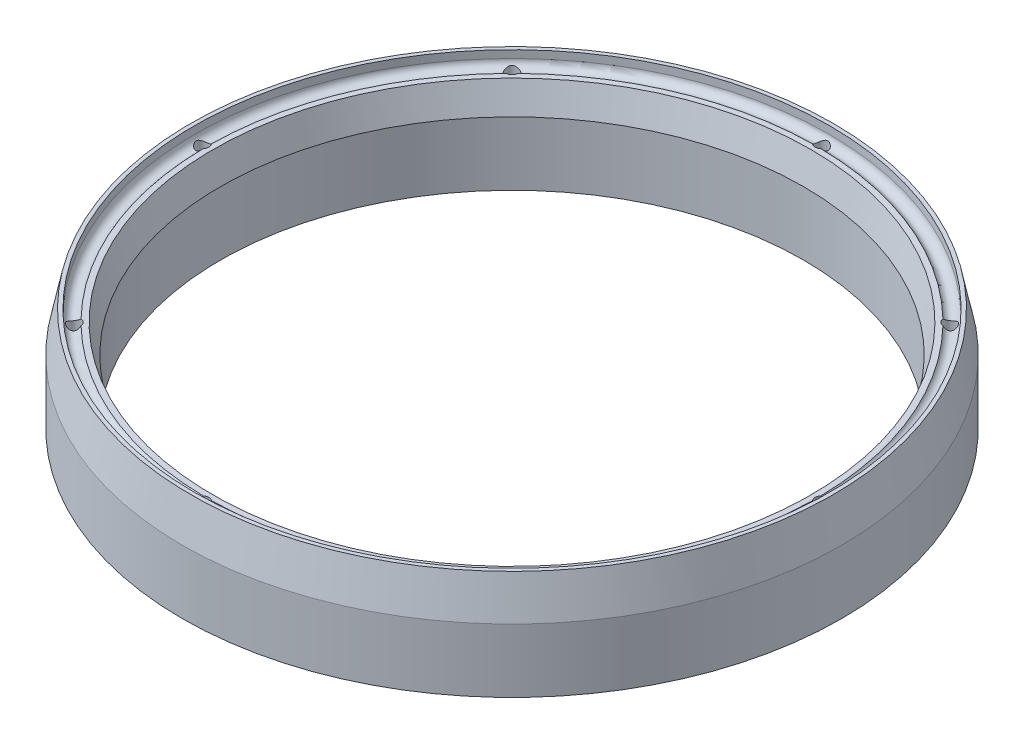
SolidWorks part; units mm, degrees
ref_plane "Front" through (0, 0, 0) normal (0, 0, 1) x (1, 0, 0)
ref_plane "Top" through (0, 0, 0) normal (0, 1, 0) x (1, 0, 0)
ref_plane "Right" through (0, 0, 0) normal (1, 0, 0) x (0, 0, -1)
sketch "Sketch3" plane through (0, 0, 0) normal (0, 0, 1) x (1, 0, 0)
  line L0 (86.2847, 16.6445) -> (86.2847, 0)
  line L1 (76.2847, 0) -> (0, 0) construction
  line L3 (76.2847, 0) -> (76.2847, 16.6445)
  line L4 (0, 0) -> (0, 10) construction
  line L5 (81.2847, 25.0416) -> (81.2847, 0) construction
  line L6 (76.2847, 16.6445) -> (78.5347, 25.0416)
  line L7 (78.5347, 25.0416) -> (84.0347, 25.0416)
  line L8 (76.2847, 0) -> (86.2847, 0)
  line L9 (84.0347, 25.0416) -> (86.2847, 16.6445)
  circle A0 centre (81.2847, 25.0416) radius 1.7653 construction
  circle A1 centre (0, 213.2) radius 203.2 construction
  dimension "D4" = 406.4
  dimension "D6" = 10
  dimension "D2" = 3.5306
  dimension "D3" = 166.1
  dimension "D5" = 5.5
  dimension "D7" = 30
  dimension "D8" = 0
  dimension "D10" = 10
revolve "Revolve1" add sketch "Sketch3" angle 360 about L4
sketch "Sketch8" plane through (0, 0, 0) normal (0, 0, 1) x (1, 0, 0)
  line L0 (0, 0) -> (0, 25.0416) construction
  line L2 (84.0347, 25.0416) -> (78.5347, 25.0416)
  line L3 (-78.6871, 24.8918) -> (-83.1871, 24.8918)
  line L4 (78.5347, 25.0416) -> (-78.5347, 25.0416) construction
  line L5 (84.0347, 25.0416) -> (78.5347, 25.0416) construction
  circle A0 centre (81.2847, 25.0416) radius 1.825
  dimension "D1" = 3.65
revolve "Cut-Revolve1" cut sketch "Sketch8" angle 360 about L0
sketch "Sketch15" plane through (0, 0, 0) normal (0, 0, 1) x (1, 0, 0)
  line L0 (81.2847, 25.0416) -> (78.5347, 25.0416)
  line L1 (78.5347, 25.0416) -> (84.0347, 25.0416) construction
  line L2 (78.5347, 25.0416) -> (78.2668, 24.0416)
  line L3 (76.2847, 16.6445) -> (78.5347, 25.0416) construction
  line L4 (78.2668, 24.0416) -> (81.2847, 24.0416)
  line L5 (81.2847, 25.0416) -> (81.2847, 0) construction
  line L6 (81.2847, 24.0416) -> (81.2847, 25.0416)
  line L7 (0, 0) -> (0, 25.0416) construction
  line L8 (78.5347, 25.0416) -> (-78.5347, 25.0416) construction
  dimension "D1" = 1
revolve "Cut-Revolve3" cut sketch "Sketch15" angle 360 about L7
sketch "Sketch17" plane through (0, 0, 0) normal (0, 0, 1) x (1, 0, 0)
  line L1 (84.1097, 27.0416) -> (83.1097, 27.0416)
  line L2 (83.1097, 27.0416) -> (83.1097, 25.0416)
  line L3 (78.5347, 25.0416) -> (84.0347, 25.0416) construction
  line L4 (83.1097, 25.0416) -> (84.0347, 25.0416)
  line L5 (86.2847, 16.6445) -> (84.1097, 27.0416)
  line L6 (84.0347, 25.0416) -> (86.2847, 16.6445)
  line L7 (0, 0) -> (0, 25.0416) construction
  circle A0 centre (81.2847, 25.0416) radius 1.825 construction
  dimension "D1" = 1
  dimension "D2" = 2
revolve "Revolve3" add sketch "Sketch17" angle 360 about L7
fillet "Fillet1" [suppressed] radius 1
hole_wizard "M4x0.7 Tapped Hole1" positions "Sketch9" profile "Sketch10" tap size "M4x0.7" standard "ANSI Metric" end condition through all
sketch "Sketch9" plane through (0, 0, 0) normal (0, -1, 0) x (-1, 0, 0)
  line L0 (-81, 0) -> (0, 0) construction
  circle A0 centre (0, 0) radius 81
  point P0 (0, -81)
  dimension "D1" = 162
cosmetic thread "Hole Thread1" [suppressed] parameters "D2"=4
sketch "Sketch10" plane through (0, 0, 81) normal (1, 0, 0) x (0, 0, -1)
  line L0 (0, 0) -> (0, 27.0416)
  line L1 (0, 27.0416) -> (1.65, 27.0416)
  line L2 (1.65, 27.0416) -> (1.65, 0)
  line L5 (1.65, 0) -> (0, 0)
  line L11 (0, -6.35) -> (0, 107.95) construction
  dimension "Thru Tap Drill Dia." = 3.3
  dimension "Thru Tap Drill Depth" = 27.0416
pattern_circular "CirPattern1" count 8 over 360 about axis through (0, 0, 0) along (0, -1, 0) of "M4x0.7 Tapped Hole1"
sketch "Sketch11" plane through (0, 0, 0) normal (0, 0, 1) x (1, 0, 0)
  line L0 (76.2847, 0) -> (71.2847, -60)
  line L1 (71.2847, -60) -> (91.2847, -60)
  line L2 (91.2847, -60) -> (86.2847, 0)
  line L3 (81.2847, 0) -> (81.2847, -60) construction
  line L4 (0, 0) -> (0, 10) construction
  line L5 (76.2847, 0) -> (86.2847, 0)
  dimension "D1" = 60
  dimension "D2" = 20
revolve "Revolve2" [suppressed] add sketch "Sketch11" angle 360 about L4
fillet "Fillet14" [suppressed] type full round
sketch "Sketch12" [suppressed] plane through (0, 0, 0) normal (0, 0, 1) x (1, 0, 0)
  line L0 (0, 0) -> (0, -60) construction
  line L2 (-17.5, 0) -> (17.5, 0)
  line L3 (86.7347, 0) -> (-86.7347, 0) construction
  line L4 (76.7347, 0) -> (0, 0) construction
  line L5 (17.5, 0) -> (28.0796, -60)
  line L6 (28.0796, -60) -> (-28.0796, -60)
  line L7 (-28.0796, -60) -> (-17.5, 0)
  dimension "D1" = 35
  dimension "D2" = 80
  dimension "D3" = 60
extrude "Cut-Extrude1" [suppressed] cut sketch "Sketch12" along normal through all
pattern_circular "CirPattern2" [suppressed] count 6 over 360 of bodies 118
fillet "Fillet2" [suppressed] type full round
fillet "Fillet5" [suppressed] type full round
fillet "Fillet6" [suppressed] type full round
fillet "Fillet7" [suppressed] type full round
fillet "Fillet8" [suppressed] type full round
fillet "Fillet9" [suppressed] type full round
fillet "Fillet3" [suppressed] radius 16
fillet "Fillet11" [suppressed] type full round
fillet "Fillet12" [suppressed] type full round
fillet "Fillet15" [suppressed] type full round
fillet "Fillet16" [suppressed] type full round
fillet "Fillet17" [suppressed] type full round
fillet "Fillet18" [suppressed] type full round
fillet "Fillet19" [suppressed] radius 10
sketch "Sketch13" [suppressed] plane through (0, 0, 0) normal (0, 0, 1) x (1, 0, 0)
  line L0 (79.4835, 25.2429) -> (-79.4835, 25.2429) construction
  line L1 (-86.7347, 25.3867) -> (86.7347, 25.3867)
  line L2 (-86.7347, 25.3867) -> (-86.7347, 17.9226)
  line L3 (-86.7347, 17.9226) -> (86.7347, 17.9226)
  line L4 (86.7347, 25.3867) -> (86.7347, 17.9226)
  line L5 (0, 17.9226) -> (0, 25.3867) construction
  line L6 (-86.7347, 21.6546) -> (86.7347, 21.6546) construction
  point P396 (0, 21.6546)
extrude "Cut-Extrude2" [suppressed] cut sketch "Sketch13" against normal through all both and the other way through all flip side to cut
sketch "Sketch14" plane through (0, 0, 0) normal (0, 0, 1) x (1, 0, 0)
  line L0 (0, 0) -> (0, 25.574) construction
  line L1 (78.6097, 25.574) -> (-78.6097, 25.574) construction
  line L2 (78.5347, 25.0416) -> (84.0347, 25.0416) construction
  line L3 (76.2847, 0) -> (86.2847, 0)
  line L4 (76.2847, 0) -> (76.2847, 21.0416)
  line L5 (76.2847, 21.0416) -> (86.2847, 21.0416)
  line L6 (86.2847, 0) -> (86.2847, 21.0416)
  line L7 (81.2847, 21.0416) -> (81.2847, 0) construction
  line L8 (76.2847, 10.5208) -> (86.2847, 10.5208) construction
  point P9 (86.2347, 0)
  point P173 (81.2847, 10.5208)
  dimension "D1" = 4
revolve "Cut-Revolve2" [suppressed] cut sketch "Sketch14" angle 360 about L0
